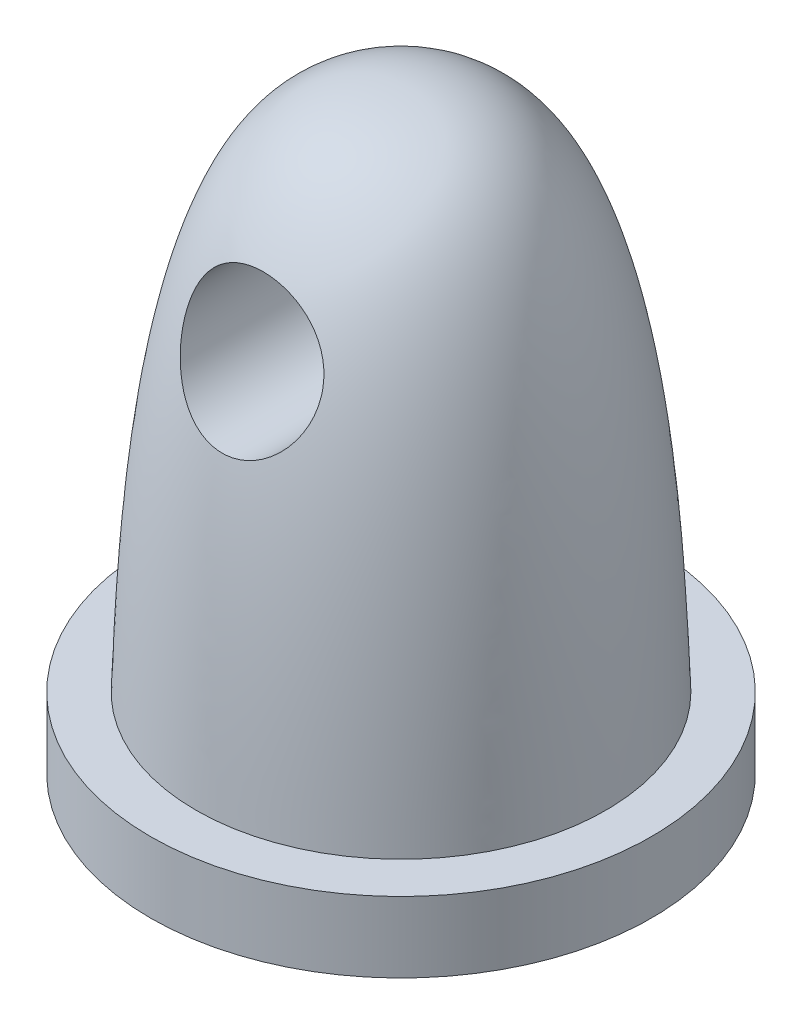
SolidWorks part; units mm, degrees
ref_plane "Front Plane" through (0, 0, 0) normal (0, 0, 1) x (1, 0, 0)
ref_plane "Top Plane" through (0, 0, 0) normal (0, 1, 0) x (1, 0, 0)
ref_plane "Right Plane" through (0, 0, 0) normal (1, 0, 0) x (0, 0, -1)
sketch "Sketch1" plane through (0, 0, 0) normal (0, 1, 0) x (1, 0, 0)
  circle A0 centre (0, 0) radius 5.5
  dimension "D1" = 11
extrude "Boss-Extrude1" add sketch "Sketch1" along normal blind 1.55
sketch "Sketch2" plane through (0, 1.55, 0) normal (0, 1, 0) x (1, 0, 0)
  circle A0 centre (0, 0) radius 4.5
  dimension "D1" = 9
extrude "Boss-Extrude2" add sketch "Sketch2" along normal blind 11.5
ref_axis "Axis1" through (0, 13.7025, 0) along (0, -1, 0)
sketch "Sketch3" plane through (0, 0, 0) normal (0, 0, 1) x (1, 0, 0)
  line L0 (0, 13.05) -> (0, 0) construction
  line L1 (0, 13.05) -> (0, 13.3793)
  line L3 (0, 13.7025) -> (0, -0.6525) construction
  line L4 (0, 13.3793) -> (-5.0638, 13.3793)
  line L5 (-5.0638, 13.3793) -> (-5.0638, 1.55)
  line L6 (5.5, 1.55) -> (-5.5, 1.55) construction
  line L7 (-5.0638, 1.55) -> (-4.5, 1.55)
  spline S0 degree 3 poles (-4.5, 1.55) (-4.4182, 3.5336) (-4.2581, 10.3205) (-1.7214, 13.0436) (0, 13.05) knots 0 0 0 0 0.654562 1 1 1 1
revolve "Cut-Revolve7" cut sketch "Sketch3" angle 360 about axis through (0, 13.7025, 0) along (0, -1, 0)
sketch "Sketch4" plane through (0, 0, 0) normal (0, 0, 1) x (1, 0, 0)
  line L0 (0, 13.7025) -> (0, -0.6525) construction
  circle A0 centre (0, 9.55) radius 1.5
  dimension "D1" = 3
  dimension "D2" = 3.5
extrude "Cut-Extrude1" cut sketch "Sketch4" against normal mid plane 10
